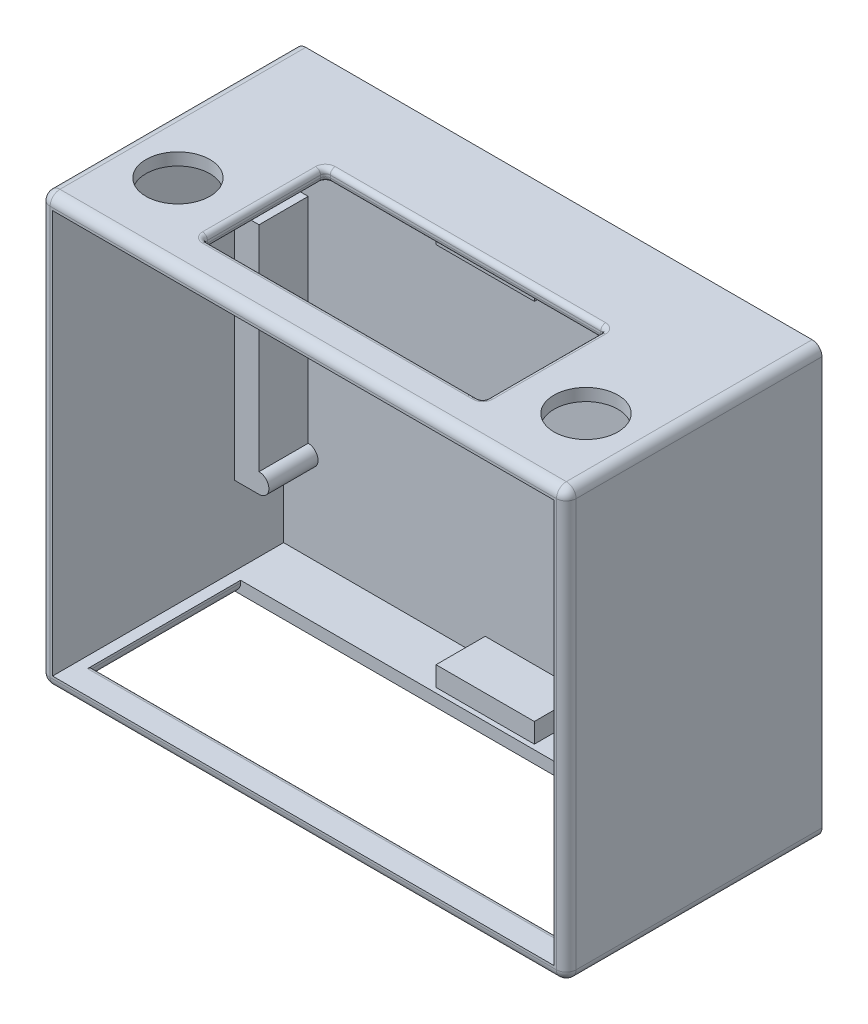
SolidWorks part; units mm, degrees
ref_plane "정면" through (0, 0, 0) normal (0, 0, 1) x (1, 0, 0)
ref_plane "윗면" through (0, 0, 0) normal (0, 1, 0) x (1, 0, 0)
ref_plane "우측면" through (0, 0, 0) normal (1, 0, 0) x (0, 0, -1)
sketch "스케치1" plane through (0, 0, 0) normal (0, 0, 1) x (1, 0, 0)
  line L1 (-53.5, -43.5) -> (53.5, -43.5)
  line L2 (-53.5, -43.5) -> (-53.5, 43.5)
  line L3 (-53.5, 43.5) -> (53.5, 43.5)
  line L4 (53.5, -43.5) -> (53.5, 43.5)
  line L5 (-53.5, -43.5) -> (53.5, 43.5) construction
  line L6 (-53.5, 43.5) -> (53.5, -43.5) construction
  point P0 (0, 0)
  dimension "D1" = 107
  dimension "D2" = 87
extrude "보스-돌출1" add sketch "스케치1" along normal blind 60
sketch "스케치2" plane through (0, 0, 60) normal (0, 0, 1) x (1, 0, 0)
  line L1 (-51, -41) -> (51, -41)
  line L2 (-51, -41) -> (-51, 41)
  line L3 (-51, 41) -> (51, 41)
  line L4 (51, -41) -> (51, 41)
  line L5 (-51, -41) -> (51, 41) construction
  line L6 (-51, 41) -> (51, -41) construction
  point P0 (0, 0)
  dimension "D1" = 102
  dimension "D2" = 82
extrude "컷-돌출1" cut sketch "스케치2" against normal blind 55
sketch "스케치3" plane through (0, -43.5, 0) normal (0, -1, 0) x (1, 0, 0)
  line L0 (-53.5, 30) -> (53.5, 30) construction
  line L1 (-48.75, 16) -> (48.75, 16)
  line L2 (-48.75, 16) -> (-48.75, 46)
  line L3 (-48.75, 46) -> (48.75, 46)
  line L4 (48.75, 16) -> (48.75, 46)
  line L5 (-53.5, 60) -> (53.5, 60) construction
  line L6 (0, 0) -> (0, 60) construction
  line L7 (-53.5, 60) -> (-53.5, 0) construction
  line L8 (53.5, 60) -> (53.5, 0) construction
  point P18 (0, 16)
  dimension "D1" = 97.5
  dimension "D2" = 30
  dimension "D4" = 14
extrude "컷-돌출2" cut sketch "스케치3" against normal blind 12
sketch "스케치4" plane through (0, 43.5, 0) normal (0, 1, 0) x (1, 0, 0)
  line L3 (53.5, 0) -> (-53.5, 0) construction
  line L4 (-53.5, -60) -> (-53.5, 0) construction
  line L5 (53.5, -60) -> (53.5, 0) construction
  circle A0 centre (-41.5, -36) radius 6.5
  circle A1 centre (41.5, -36) radius 6.5
  dimension "D1" = 13
  dimension "D2" = 13
  dimension "D3" = 36
  dimension "D4" = 12
  dimension "D5" = 12
  dimension "D6" = 36
extrude "컷-돌출3" cut sketch "스케치4" against normal blind 12
ref_plane "평면1" through (0, 0, 10) normal (0, 0, 1) x (1, 0, 0)
sketch "스케치6" plane through (0, 0, 10) normal (0, 0, 1) x (1, 0, 0)
  line L0 (51, 41) -> (-51, 41) construction
  line L1 (-10, 41) -> (10, 41)
  line L2 (-10, 41) -> (-10, 37)
  line L3 (-10, 37) -> (10, 37)
  line L4 (10, 41) -> (10, 37)
  line L5 (51, -41) -> (51, 41) construction
  line L6 (51, 22.5) -> (46, 22.5)
  line L7 (51, 22.5) -> (51, -22.5)
  line L8 (51, -22.5) -> (46, -22.5)
  line L9 (46, 22.5) -> (46, -22.5)
  line L10 (-51, -41) -> (51, -41) construction
  line L11 (10, -41) -> (-10, -41)
  line L12 (10, -41) -> (10, -37)
  line L13 (10, -37) -> (-10, -37)
  line L14 (-10, -41) -> (-10, -37)
  line L15 (-51, 41) -> (-51, -41) construction
  line L16 (-51, -22.5) -> (-46, -22.5)
  line L17 (-51, -22.5) -> (-51, 22.5)
  line L18 (-51, 22.5) -> (-46, 22.5)
  line L19 (-46, -22.5) -> (-46, 22.5)
  line L20 (51, 0) -> (-51, 0) construction
  line L21 (0, 41) -> (0, -41) construction
  dimension "D1" = 45
  dimension "D2" = 5
  dimension "D3" = 5
  dimension "D4" = 20
  dimension "D5" = 4
  dimension "D6" = 4
extrude "보스-돌출2" add sketch "스케치6" along normal blind 5 and the other way blind 10
sketch "스케치7" plane through (0, 0, 10) normal (0, 0, 1) x (1, 0, 0)
  line L0 (-46, -21) -> (-50, -21)
  line L1 (-51, 41) -> (51, 41) construction
  line L2 (-51, 41) -> (-51, -41) construction
  line L3 (-51, -41) -> (51, -41) construction
  line L4 (51, 41) -> (51, -41) construction
  line L5 (-50, 40) -> (50, 40) construction
  line L6 (-50, 40) -> (-50, -40) construction
  line L7 (-50, -40) -> (50, -40) construction
  line L8 (50, 40) -> (50, -40) construction
  line L9 (0, 40) -> (0, -40) construction
  line L10 (-50, 0) -> (50, 0) construction
  line L11 (-34.5, 38) -> (-34.5, 41)
  line L12 (39, 40) -> (50, 40) construction
  line L13 (39, 40) -> (39, 24) construction
  line L14 (39, 24) -> (50, 24) construction
  line L15 (50, 40) -> (50, 24) construction
  line L16 (-40, 40) -> (-32, 40) construction
  line L17 (-40, 40) -> (-40, 36) construction
  line L18 (-40, 36) -> (-32, 36) construction
  line L19 (-32, 40) -> (-32, 36) construction
  line L20 (-37.5, 38) -> (-37.5, 41)
  line L21 (-46, -25) -> (-51, -25)
  line L22 (-50, -21) -> (-46, -22.5)
  line L23 (-46, -22.5) -> (-51, -22.5)
  line L24 (-51, -22.5) -> (-51, -25)
  line L25 (42, -24) -> (50, -24)
  line L26 (42, -28) -> (51, -28)
  line L27 (51, -28) -> (51, -22.5)
  line L28 (46, -22.5) -> (50, -24)
  line L29 (51, -22.5) -> (51, 22.5) construction
  line L30 (46, -22.5) -> (51, -22.5)
  line L31 (44.5, 36) -> (44.5, 41)
  line L32 (44.5, 28) -> (51, 28)
  line L33 (-37.5, 41) -> (-34.5, 41)
  line L34 (44.5, 41) -> (51, 41)
  line L35 (51, 41) -> (51, 28)
  arc A0 (-46, -25) -> (-46, -21) centre (-46, -23) ccw
  arc A1 (42, -24) -> (42, -28) centre (42, -26) ccw
  arc A2 (44.5, 36) -> (44.5, 28) centre (44.5, 32) ccw
  arc A3 (-37.5, 38) -> (-34.5, 38) centre (-36, 38) ccw
  dimension "D3" = 4
  dimension "D4" = 4
  dimension "D10" = 8
  dimension "D16" = 8
  dimension "D17" = 3
  dimension "D1" = 100
  dimension "D2" = 80
  dimension "D5" = 17
  dimension "D6" = 4
  dimension "D7" = 14
  dimension "D8" = 8
  dimension "D9" = 8
  dimension "D11" = 5.5
  dimension "D12" = 16
  dimension "D13" = 11
  dimension "D14" = 10
  dimension "D15" = 4
  dimension "D18" = 4
  dimension "D19" = 2
extrude "보스-돌출3" add sketch "스케치7" along normal blind 5 and the other way blind 10
sketch "스케치10" plane through (0, -43.5, 0) normal (0, -1, 0) x (1, 0, 0)
  line L0 (53.5, 60) -> (53.5, 0) construction
  line L1 (-53.5, 60) -> (53.5, 60)
  line L2 (-53.5, 60) -> (-53.5, 52)
  line L3 (-53.5, 52) -> (53.5, 52)
  line L4 (53.5, 60) -> (53.5, 52)
  dimension "D1" = 8
extrude "컷-돌출4" cut sketch "스케치10" against normal through all
fillet "필렛1" radius 2 10 edges at (53.5, 43.5, 26) (53.5, -43.5, 26) (0, -43.5, 46) (-53.5, 43.5, 26) (-53.5, -43.5, 26) (-48.75, -43.5, 31) (0, -43.5, 52) (53.5, 0, 52) (-53.5, 0, 52) (0, 43.5, 52)
sketch "스케치11" plane through (0, 43.5, 0) normal (0, 1, 0) x (1, 0, 0)
  line L0 (51.5, -52) -> (-51.5, -52) construction
  line L1 (-28.5, -44) -> (28.5, -44)
  line L2 (-28.5, -44) -> (-28.5, -19)
  line L3 (-28.5, -19) -> (28.5, -19)
  line L4 (28.5, -44) -> (28.5, -19)
  line L5 (-28.5, -44) -> (28.5, -19) construction
  line L6 (-28.5, -19) -> (28.5, -44) construction
  line L7 (0, 0) -> (0, -52) construction
  line L8 (51.5, 0) -> (-51.5, 0) construction
  point P0 (0, -31.5)
  dimension "D1" = 8
  dimension "D2" = 25
  dimension "D3" = 57
extrude "컷-돌출5" cut sketch "스케치11" against normal blind 10
fillet "필렛2" radius 1 13 edges at (28.5, 41, 31.5) (-28.5, 41, 31.5) (-28.5, 43.5, 31.5) (28.5, 43.5, 31.5) (0, 41, 44) (28.5, 42.25, 44) (0, 43.5, 44) (-28.5, 42.25, 44) (0, 41, 19) (-28.5, 42.25, 19) (0, 43.5, 19) (28.5, 42.25, 19) (0, -41, 46)
